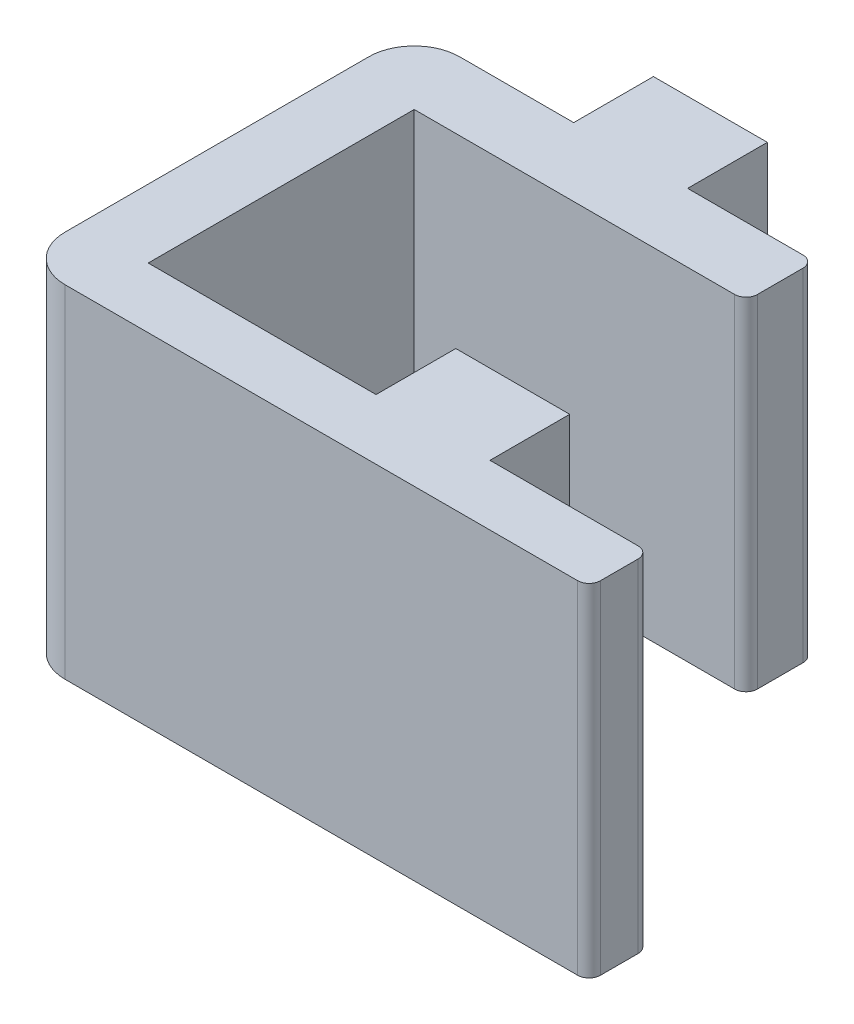
SolidWorks part; units mm, degrees
ref_plane "Front Plane" through (0, 0, 0) normal (0, 0, 1) x (1, 0, 0)
ref_plane "Top Plane" through (0, 0, 0) normal (0, 1, 0) x (1, 0, 0)
ref_plane "Right Plane" through (0, 0, 0) normal (1, 0, 0) x (0, 0, -1)
sketch "Sketch1" plane through (0, 0, 0) normal (0, 1, 0) x (1, 0, 0)
  line L1 (0, 0) -> (-25, 0)
  line L2 (0, 0) -> (0, 2.65)
  line L3 (0, 2.65) -> (-22, 2.65)
  line L6 (-25, 0) -> (-25, 17.325)
  line L8 (-22, 2.65) -> (-22, 14.325)
  line L9 (-25, 17.325) -> (-7.4355, 17.325)
  line L11 (-22, 14.325) -> (-7.4355, 14.325)
  line L12 (-7.4355, 17.325) -> (-7.4355, 14.325)
  dimension "D1" = 2.65
  dimension "D2" = 17.325
  dimension "D3" = 25
  dimension "D4" = 3
  dimension "D5" = 3
extrude "Boss-Extrude1" add sketch "Sketch1" along normal blind 15
sketch "Sketch2" plane through (0, 0, -2.65) normal (0, 0, -1) x (-1, 0, 0)
  line L0 (0, 0) -> (22, 0) construction
  line L1 (12, 0) -> (7, 0)
  line L2 (12, 0) -> (12, 15)
  line L3 (12, 15) -> (7, 15)
  line L4 (7, 0) -> (7, 15)
  line L5 (0, 15) -> (22, 15) construction
  line L6 (22, 15) -> (22, 0) construction
  dimension "D1" = 10
  dimension "D2" = 5
extrude "Boss-Extrude2" add sketch "Sketch2" along normal blind 3.5
sketch "Sketch3" plane through (0, 0, -17.325) normal (0, 0, -1) x (-1, 0, 0)
  line L0 (7.4355, 0) -> (25, 0) construction
  line L1 (18, 0) -> (13, 0)
  line L2 (18, 0) -> (18, 15)
  line L3 (18, 15) -> (13, 15)
  line L4 (13, 0) -> (13, 15)
  line L5 (7.4355, 15) -> (25, 15) construction
  line L6 (25, 15) -> (25, 0) construction
  dimension "D1" = 7
  dimension "D2" = 5
extrude "Boss-Extrude3" add sketch "Sketch3" along normal blind 3.5
fillet "Fillet1" radius 2 2 edges at (-25, 7.5, 0) (-25, 7.5, -17.325)
fillet "Fillet2" radius 0.5 4 edges at (-7.4355, 7.5, -17.325) (-7.4355, 7.5, -14.325) (0, 7.5, 0) (0, 7.5, -2.65)
